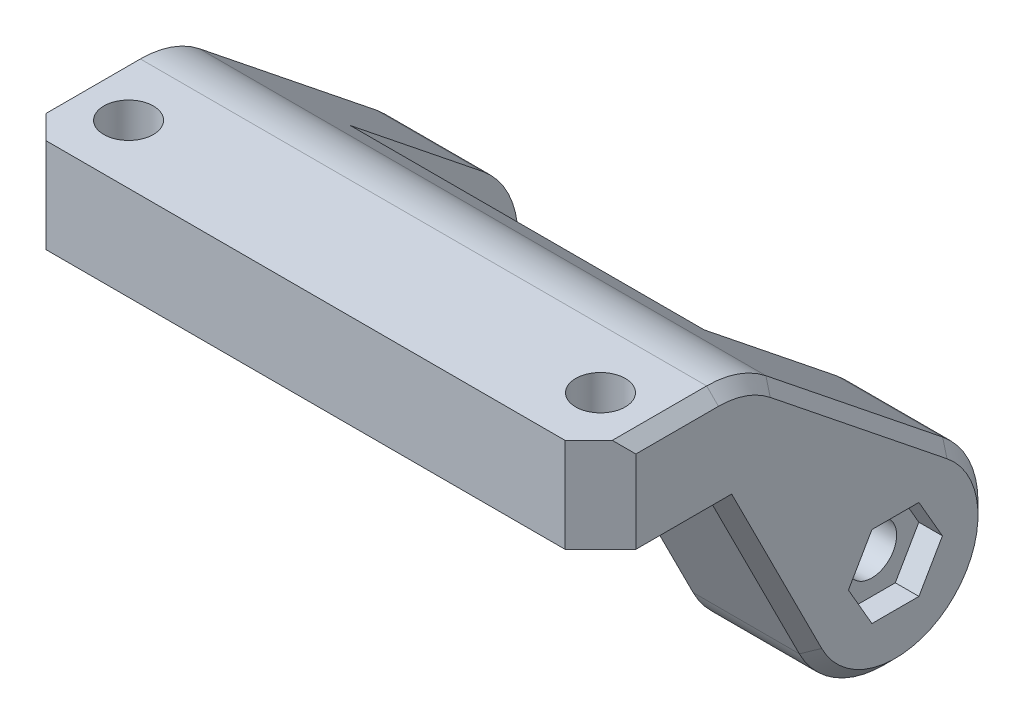
SolidWorks part; units mm, degrees
ref_plane "Alzado" through (0, 0, 0) normal (0, 0, 1) x (1, 0, 0)
ref_plane "Planta" through (0, 0, 0) normal (0, 1, 0) x (1, 0, 0)
ref_plane "Vista lateral" through (0, 0, 0) normal (1, 0, 0) x (0, 0, -1)
sketch "Croquis1" plane through (0, 0, 0) normal (0, 1, 0) x (1, 0, 0)
  line L0 (0, 0) -> (0, 17830.0329) construction
  line L1 (-25, 5) -> (25, 5)
  line L2 (25, 5) -> (25, -5)
  line L3 (25, -5) -> (-25, -5)
  line L4 (0, 0) -> (17830.0329, 0) construction
  line L5 (-25, 5) -> (-25, -5)
  circle A0 centre (20, 0) radius 2.1
  circle A1 centre (-20, 0) radius 2.1
  point P7 (20, 0)
  point P12 (25, 0)
  point P13 (0, -5)
  point P17 (0, -5)
  point P18 (0, 5)
  dimension "D1" = 40
  dimension "D2" = 4.2
  dimension "D3" = 10
  dimension "D4" = 50
extrude "Saliente-Extruir1" add sketch "Croquis1" along normal blind 8
sketch "Croquis4" plane through (0, 0, 0) normal (1, 0, 0) x (0, 0, -1)
  line L1 (5, 8) -> (5, 0)
  line L2 (12.8548, -15.5981) -> (5, 0)
  line L3 (24.9996, -5.7547) -> (10.0177, 6.239)
  line L4 (-5, 8) -> (5, 8) construction
  circle A0 centre (20, -12) radius 2.1
  arc A1 (12.8548, -15.5981) -> (24.9996, -5.7547) centre (20, -12) ccw
  arc A2 (5, 8) -> (10.0177, 6.239) centre (5, -0.0289) cw
  point P10 (7.4122, -7.0909)
  point P11 (12.5733, 6.306)
  point P15 (10.0177, 6.239)
  dimension "D1" = 8
  dimension "D2" = 4.2
  dimension "D3" = 20
  dimension "D4" = 20
extrude "Saliente-Extruir2" add sketch "Croquis4" along normal mid plane 50
sketch "Croquis5" plane through (0, 0, 0) normal (1, 0, 0) x (0, 0, -1)
  circle A0 centre (20, -12) radius 15.8005
extrude "Cortar-Extruir1" cut sketch "Croquis5" against normal mid plane 30
sketch "Croquis6" plane through (-25, 0, 0) normal (-1, 0, 0) x (0, 0, 1)
  line L1 (-16.0163, -12) -> (-18.0081, -8.55)
  line L2 (-18.0081, -8.55) -> (-21.9919, -8.55)
  line L3 (-21.9919, -8.55) -> (-23.9837, -12)
  line L4 (-23.9837, -12) -> (-21.9919, -15.45)
  line L5 (-21.9919, -15.45) -> (-18.0081, -15.45)
  line L6 (-18.0081, -15.45) -> (-16.0163, -12)
  circle A0 centre (-20, -12) radius 3.45 construction
  dimension "D1" = 6.9
extrude "Cortar-Extruir2" cut sketch "Croquis6" against normal mid plane 4
mirror "Simetría1" about plane through (0, 0, 0) normal (1, 0, 0) of "Cortar-Extruir2"
chamfer "Chaflán1" distance 3 angle 45 2 edges at (25, 4, 5) (-25, 4, 5)
sketch "Croquis7" plane through (0, 0, 0) normal (0, -1, 0) x (1, 0, 0)
  line L1 (-16.0163, 0) -> (-18.0081, 3.45)
  line L2 (-18.0081, 3.45) -> (-21.9919, 3.45)
  line L3 (-21.9919, 3.45) -> (-23.9837, 0)
  line L4 (-23.9837, 0) -> (-21.9919, -3.45)
  line L5 (-21.9919, -3.45) -> (-18.0081, -3.45)
  line L6 (-18.0081, -3.45) -> (-16.0163, 0)
  line L7 (0, 0) -> (0, 50000) construction
  line L8 (18.0081, -3.45) -> (16.0163, 0)
  line L9 (21.9919, -3.45) -> (18.0081, -3.45)
  line L10 (23.9837, 0) -> (21.9919, -3.45)
  line L11 (21.9919, 3.45) -> (23.9837, 0)
  line L12 (18.0081, 3.45) -> (21.9919, 3.45)
  line L13 (16.0163, 0) -> (18.0081, 3.45)
  circle A0 centre (-20, 0) radius 3.45 construction
  circle A1 centre (20, 0) radius 3.45 construction
  dimension "D1" = 6.9
extrude "Cortar-Extruir3" cut sketch "Croquis7" against normal mid plane 4
chamfer "Chaflán2" distance 1 angle 45 12 edges at (0, -3.4285, -6.7265) (0, 2.7606, -14.3627) (25, 8, -1.5) (25, 7.547, -7.6589) (25, -7.7991, -8.9274) (25, 0.2421, -17.5086) (25, -18.215, -25.0373) (-25, 8, -1.5) (-25, 7.547, -7.6589) (-25, -7.7991, -8.9274) (-25, 0.2421, -17.5086) (-25, -18.215, -25.0373) first distance on face at (0, -0.0295, -10.2978) first distance on face at (0, 8, 0.6667) first distance on face at (0, 7.3332, -7.5838) first distance on face at (0, -8.6562, -9.359) first distance on face at (0, -0.6275, -18.5949) first distance on face at (20, -14.4457, -21.9822) first distance on face at (-25, -12, -20)
